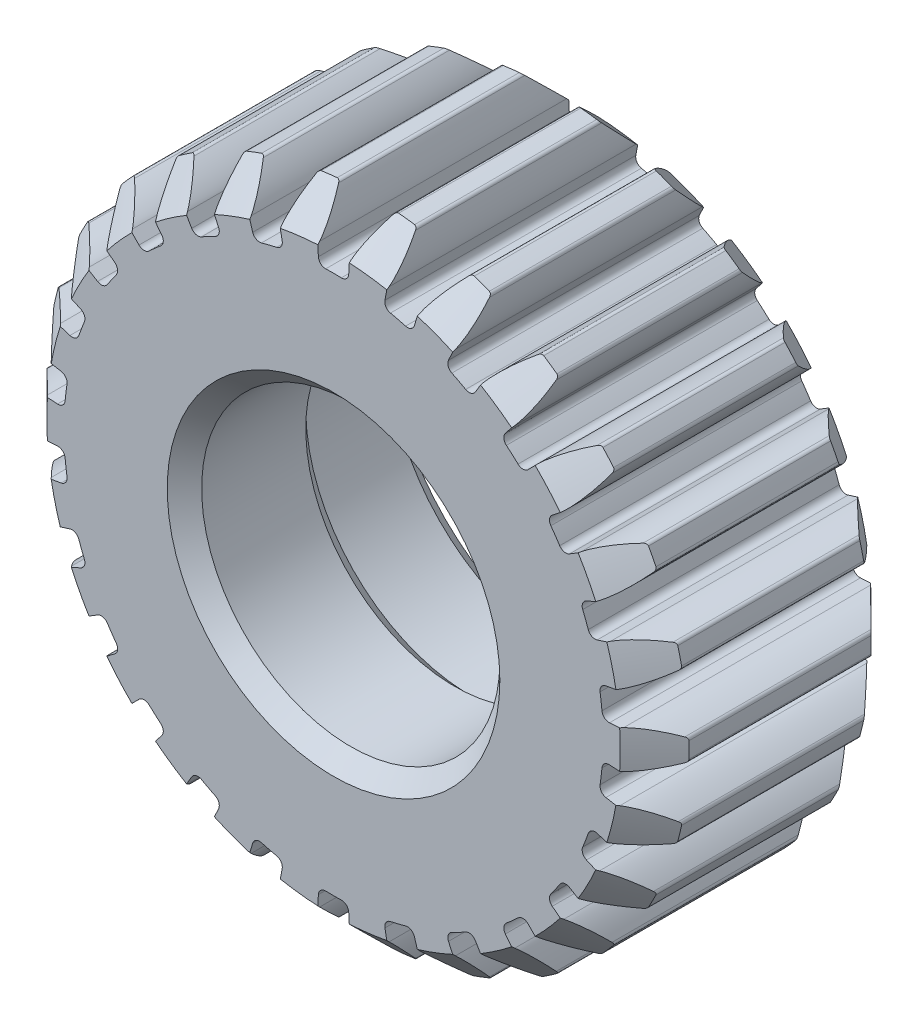
SolidWorks part; units mm, degrees
material "ABS"
ref_plane "Front" through (0, 0, 0) normal (0, 0, 1) x (1, 0, 0)
ref_plane "Top" through (0, 0, 0) normal (0, 1, 0) x (1, 0, 0)
ref_plane "Right" through (0, 0, 0) normal (1, 0, 0) x (0, 0, -1)
sketch "Sketch1" plane through (0, 0, 0) normal (0, 0, 1) x (1, 0, 0)
  circle A0 centre (0, 0) radius 14.224
  dimension "OutsideDiameter" = 28.448
extrude "Boss-Extrude1" add sketch "Sketch1" along normal blind 11.1125
sketch "Sketch3" plane through (0, 0, 0) normal (0, 0, 1) x (1, 0, 0)
  line L0 (0, 0) -> (43.7181, 0) construction
  line L2 (0, 0) -> (-0.6547, 11.92) construction
  line L3 (0, 0) -> (0.6547, 11.92) construction
  line L4 (0.6547, 11.92) -> (0.7013, 12.768) construction
  line L5 (0, 0) -> (0, 61.276) construction
  line L6 (-0.6547, 11.92) -> (-0.7013, 12.768) construction
  circle A0 centre (0, 0) radius 14.224 construction
  circle A1 centre (0, 0) radius 13.208 construction
  circle A2 centre (0, 0) radius 12.7873 construction
  arc A3 (0.6547, 11.92) -> (-0.6547, 11.92) centre (0, 0) ccw construction
  arc A5 (1.2601, 14.1681) -> (-1.2601, 14.1681) centre (0, 0) ccw
  spline S0 degree 4 poles (-0.7013, 12.768) (-0.7014, 12.7703) (-0.7019, 12.7766) (-0.7031, 12.7884) (-0.7055, 12.8077) (-0.709, 12.8323) (-0.7143, 12.864) (-0.7215, 12.9013) (-0.7302, 12.9422) (-0.7407, 12.9866) (-0.752, 13.0308) (-0.7641, 13.0749) (-0.777, 13.1187) (-0.7933, 13.1717) (-0.8142, 13.2351) (-0.8403, 13.3091) (-0.872, 13.3928) (-0.9064, 13.4778) (-0.9422, 13.5612) (-0.9804, 13.6452) (-1.0189, 13.7264) (-1.061, 13.8104) (-1.1009, 13.8878) (-1.148, 13.9742) (-1.1867, 14.0438) (-1.2403, 14.1353) (-1.2727, 14.1892) (-1.3115, 14.2522) (-1.3292, 14.2801) (-1.3401, 14.2973) knots 0 0 0 0 0 0.005377 0.015084 0.028532 0.04661 0.064855 0.092111 0.119476 0.146842 0.174209 0.201575 0.228941 0.256307 0.307035 0.361767 0.4165 0.471232 0.525964 0.580697 0.635429 0.690161 0.744894 0.799626 0.854358 0.909091 0.954545 1 1 1 1 1 construction
  spline S1 degree 4 poles (-0.7013, 12.768) (-0.7014, 12.7703) (-0.7019, 12.7766) (-0.7031, 12.7884) (-0.7055, 12.8077) (-0.709, 12.8323) (-0.7143, 12.864) (-0.7215, 12.9013) (-0.7302, 12.9422) (-0.7407, 12.9866) (-0.752, 13.0308) (-0.7641, 13.0749) (-0.777, 13.1187) (-0.7933, 13.1717) (-0.8142, 13.2351) (-0.8403, 13.3091) (-0.872, 13.3928) (-0.9064, 13.4778) (-0.9422, 13.5612) (-0.9804, 13.6452) (-1.0189, 13.7264) (-1.061, 13.8104) (-1.1009, 13.8878) (-1.148, 13.9742) (-1.1867, 14.0438) (-1.2287, 14.1154) (-1.2494, 14.1503) (-1.2601, 14.1681) knots 0 0 0 0 0 0.005377 0.015084 0.028532 0.04661 0.064855 0.092111 0.119476 0.146842 0.174209 0.201575 0.228941 0.256307 0.307035 0.361767 0.4165 0.471232 0.525964 0.580697 0.635429 0.690161 0.744894 0.799626 0.854358 0.909091 0.909091 0.909091 0.909091 0.909091
  spline S2 degree 4 poles (0.7013, 12.768) (0.7014, 12.7703) (0.7019, 12.7766) (0.7031, 12.7884) (0.7055, 12.8077) (0.709, 12.8323) (0.7143, 12.864) (0.7215, 12.9013) (0.7302, 12.9422) (0.7407, 12.9866) (0.752, 13.0308) (0.7641, 13.0749) (0.777, 13.1187) (0.7933, 13.1717) (0.8142, 13.2351) (0.8403, 13.3091) (0.872, 13.3928) (0.9064, 13.4778) (0.9422, 13.5612) (0.9804, 13.6452) (1.0189, 13.7264) (1.061, 13.8104) (1.1009, 13.8878) (1.148, 13.9742) (1.1867, 14.0438) (1.2403, 14.1353) (1.2727, 14.1892) (1.3115, 14.2522) (1.3292, 14.2801) (1.3401, 14.2973) knots 0 0 0 0 0 0.005377 0.015084 0.028532 0.04661 0.064855 0.092111 0.119476 0.146842 0.174209 0.201575 0.228941 0.256307 0.307035 0.361767 0.4165 0.471232 0.525964 0.580697 0.635429 0.690161 0.744894 0.799626 0.854358 0.909091 0.954545 1 1 1 1 1 construction
  spline S3 degree 4 poles (0.7013, 12.768) (0.7014, 12.7703) (0.7019, 12.7766) (0.7031, 12.7884) (0.7055, 12.8077) (0.709, 12.8323) (0.7143, 12.864) (0.7215, 12.9013) (0.7302, 12.9422) (0.7407, 12.9866) (0.752, 13.0308) (0.7641, 13.0749) (0.777, 13.1187) (0.7933, 13.1717) (0.8142, 13.2351) (0.8403, 13.3091) (0.872, 13.3928) (0.9064, 13.4778) (0.9422, 13.5612) (0.9804, 13.6452) (1.0189, 13.7264) (1.061, 13.8104) (1.1009, 13.8878) (1.148, 13.9742) (1.1867, 14.0438) (1.2287, 14.1154) (1.2494, 14.1503) (1.2601, 14.1681) knots 0 0 0 0 0 0.005377 0.015084 0.028532 0.04661 0.064855 0.092111 0.119476 0.146842 0.174209 0.201575 0.228941 0.256307 0.307035 0.361767 0.4165 0.471232 0.525964 0.580697 0.635429 0.690161 0.744894 0.799626 0.854358 0.909091 0.909091 0.909091 0.909091 0.909091
  point P0 (0, 11.938)
  dimension "OutsideDiameter" = 28.448
  dimension "PitchCircle" = 26.416
  dimension "BaseCircle" = 25.5746
  dimension "DedendumCircle" = 23.876
sketch "DCLTBC" plane through (0, 0, 0) normal (0, 0, 1) x (1, 0, 0)
  line L0 (0, 0) -> (41.04, 0) construction
  line L1 (-0.6547, 11.92) -> (-0.7013, 12.768) construction
  line L2 (0.6547, 11.92) -> (0.7013, 12.768) construction
  line L3 (-0.6547, 11.92) -> (-0.7013, 12.768)
  line L4 (0.6547, 11.92) -> (0.7013, 12.768)
  line L5 (0, 0) -> (0, 104.9356) construction
  circle A0 centre (0, 0) radius 14.224
  circle A1 centre (0, 0) radius 13.208 construction
  circle A2 centre (0, 0) radius 12.7873 construction
  arc A3 (0.6547, 11.92) -> (-0.6547, 11.92) centre (0, 0) ccw construction
  arc A4 (0.6547, 11.92) -> (-0.6547, 11.92) centre (0, 0) ccw
  spline S0 degree 4 poles (-1994.3618, -145.1347) (-17.1064, 10.8202) (-0.8523, 12.0352) (-0.6598, 12.4317) (-0.7055, 12.8077) (-0.709, 12.8323) (-0.7143, 12.864) (-0.7215, 12.9013) (-0.7302, 12.9422) (-0.7407, 12.9866) (-0.752, 13.0308) (-0.7641, 13.0749) (-0.777, 13.1187) (-0.7933, 13.1717) (-0.8142, 13.2351) (-0.8403, 13.3091) (-0.872, 13.3928) (-0.9064, 13.4778) (-0.9422, 13.5612) (-0.9804, 13.6452) (-1.0189, 13.7264) (-1.061, 13.8104) (-1.1009, 13.8878) (-1.148, 13.9742) (-1.4023, 14.4316) (-2.5651, 16.2513) (18.7364, -19.3109) (-1033.241, 1727.2731) knots -0.861068 -0.861068 -0.861068 -0.861068 -0.861068 0.005377 0.015084 0.028532 0.04661 0.064855 0.092111 0.119476 0.146842 0.174209 0.201575 0.228941 0.256307 0.307035 0.361767 0.4165 0.471232 0.525964 0.580697 0.635429 0.690161 0.744894 0.799626 0.854358 2.128331 2.128331 2.128331 2.128331 2.128331 only from (-0.7013, 12.768) to (-1.2601, 14.1681) construction
  spline S1 degree 4 poles (1994.3618, -145.1346) (17.1064, 10.8202) (0.8523, 12.0352) (0.6598, 12.4317) (0.7055, 12.8077) (0.709, 12.8323) (0.7143, 12.864) (0.7215, 12.9013) (0.7302, 12.9422) (0.7407, 12.9866) (0.752, 13.0308) (0.7641, 13.0749) (0.777, 13.1187) (0.7933, 13.1717) (0.8142, 13.2351) (0.8403, 13.3091) (0.872, 13.3928) (0.9064, 13.4778) (0.9422, 13.5612) (0.9804, 13.6452) (1.0189, 13.7264) (1.061, 13.8104) (1.1009, 13.8878) (1.148, 13.9742) (1.4023, 14.4316) (2.5651, 16.2513) (-18.7364, -19.3109) (1033.241, 1727.2731) knots -0.861068 -0.861068 -0.861068 -0.861068 -0.861068 0.005377 0.015084 0.028532 0.04661 0.064855 0.092111 0.119476 0.146842 0.174209 0.201575 0.228941 0.256307 0.307035 0.361767 0.4165 0.471232 0.525964 0.580697 0.635429 0.690161 0.744894 0.799626 0.854358 2.128331 2.128331 2.128331 2.128331 2.128331 only from (0.7013, 12.768) to (1.2601, 14.1681) construction
  spline S2 degree 4 poles (-0.7013, 12.768) (-0.7014, 12.7703) (-0.7019, 12.7766) (-0.7031, 12.7884) (-0.7055, 12.8077) (-0.709, 12.8323) (-0.7143, 12.864) (-0.7215, 12.9013) (-0.7302, 12.9422) (-0.7407, 12.9866) (-0.752, 13.0308) (-0.7641, 13.0749) (-0.777, 13.1187) (-0.7933, 13.1717) (-0.8142, 13.2351) (-0.8403, 13.3091) (-0.872, 13.3928) (-0.9064, 13.4778) (-0.9422, 13.5612) (-0.9804, 13.6452) (-1.0189, 13.7264) (-1.061, 13.8104) (-1.1009, 13.8878) (-1.148, 13.9742) (-1.1867, 14.0438) (-1.2287, 14.1154) (-1.2494, 14.1503) (-1.2601, 14.1681) knots 0 0 0 0 0 0.005377 0.015084 0.028532 0.04661 0.064855 0.092111 0.119476 0.146842 0.174209 0.201575 0.228941 0.256307 0.307035 0.361767 0.4165 0.471232 0.525964 0.580697 0.635429 0.690161 0.744894 0.799626 0.854358 0.909091 0.909091 0.909091 0.909091 0.909091
  spline S3 degree 4 poles (0.7013, 12.768) (0.7014, 12.7703) (0.7019, 12.7766) (0.7031, 12.7884) (0.7055, 12.8077) (0.709, 12.8323) (0.7143, 12.864) (0.7215, 12.9013) (0.7302, 12.9422) (0.7407, 12.9866) (0.752, 13.0308) (0.7641, 13.0749) (0.777, 13.1187) (0.7933, 13.1717) (0.8142, 13.2351) (0.8403, 13.3091) (0.872, 13.3928) (0.9064, 13.4778) (0.9422, 13.5612) (0.9804, 13.6452) (1.0189, 13.7264) (1.061, 13.8104) (1.1009, 13.8878) (1.148, 13.9742) (1.1867, 14.0438) (1.2287, 14.1154) (1.2494, 14.1503) (1.2601, 14.1681) knots 0 0 0 0 0 0.005377 0.015084 0.028532 0.04661 0.064855 0.092111 0.119476 0.146842 0.174209 0.201575 0.228941 0.256307 0.307035 0.361767 0.4165 0.471232 0.525964 0.580697 0.635429 0.690161 0.744894 0.799626 0.854358 0.909091 0.909091 0.909091 0.909091 0.909091
  dimension "OutsideDiameter" = 28.448
  dimension "PitchCircle" = 26.416
  dimension "BaseCircle" = 25.5746
extrude "Cut-Extrude-DCLTBC" cut sketch "DCLTBC" along normal through all
fillet "Fillet-Tip-DCLTBC" radius 0.1588 2 edges at (1.2601, 14.1681, 5.5562) (-1.2601, 14.1681, 5.5562)
fillet "Fillet-Root-DCLTBC" radius 0.3176 2 edges at (-0.6547, 11.92, 5.5562) (0.6547, 11.92, 5.5562)
pattern_circular "CirPattern-DCLTBC" count 26 over 360 about axis through (0, 0, 11.1125) along (0, 0, 1) of "Cut-Extrude-DCLTBC", "Fillet-Tip-DCLTBC", "Fillet-Root-DCLTBC"
sketch "DCGTBC" [suppressed] plane through (0, 0, 0) normal (0, 0, 1) x (1, 0, 0)
  line L0 (0, 0) -> (41.04, 0) construction
  line L1 (-37.3224, 3.2653) -> (0, 0) construction
  line L2 (0, 0) -> (37.3224, 3.2653) construction
  line L3 (0, 0) -> (-16.5124, 0)
  line L5 (0, 0) -> (0, 104.9356) construction
  circle A0 centre (0, 0) radius 38.608
  circle A1 centre (0, 0) radius 38.1 construction
  circle A2 centre (0, 0) radius 36.8864 construction
  arc A3 (0.1846, 37.4645) -> (-0.1846, 37.4645) centre (0, 0) ccw construction
  arc A11 (37.3224, 3.2653) -> (-37.3224, 3.2653) centre (0, 0) ccw
  spline S4 degree 4 poles (999.1092, -9.1639) (9.2917, 35.7604) (0.2917, 36.1338) (0.1647, 36.5321) (0.1834, 36.9323) (0.1852, 36.961) (0.188, 36.9982) (0.192, 37.0421) (0.197, 37.0904) (0.2032, 37.143) (0.21, 37.1956) (0.2175, 37.2482) (0.2254, 37.3006) (0.2357, 37.3641) (0.2489, 37.4405) (0.2657, 37.53) (0.2863, 37.6318) (0.309, 37.7359) (0.3327, 37.8385) (0.3583, 37.9426) (0.3842, 38.0436) (0.4127, 38.1489) (0.4399, 38.2463) (0.4722, 38.3558) (0.6183, 38.8417) (1.2009, 40.5477) (-6.8048, 15.7351) (309.5446, 989.6637) knots -0.780323 -0.780323 -0.780323 -0.780323 -0.780323 0.005377 0.015084 0.028532 0.04661 0.064855 0.092111 0.119476 0.146842 0.174209 0.201575 0.228941 0.256307 0.307035 0.361767 0.4165 0.471232 0.525964 0.580697 0.635429 0.690161 0.744894 0.799626 0.854358 1.89102 1.89102 1.89102 1.89102 1.89102 only from (0.1817, 36.886) to (0.5498, 38.6041) construction
  spline S5 degree 4 poles (-999.1092, -9.1639) (-9.2917, 35.7604) (-0.2917, 36.1338) (-0.1647, 36.5321) (-0.1834, 36.9323) (-0.1852, 36.961) (-0.188, 36.9982) (-0.192, 37.0421) (-0.197, 37.0904) (-0.2032, 37.143) (-0.21, 37.1956) (-0.2175, 37.2482) (-0.2254, 37.3006) (-0.2357, 37.3641) (-0.2489, 37.4405) (-0.2657, 37.53) (-0.2863, 37.6318) (-0.309, 37.7359) (-0.3327, 37.8385) (-0.3583, 37.9426) (-0.3842, 38.0436) (-0.4127, 38.1489) (-0.4399, 38.2463) (-0.4722, 38.3558) (-0.6183, 38.8417) (-1.2009, 40.5477) (6.8048, 15.7351) (-309.5446, 989.6637) knots -0.780323 -0.780323 -0.780323 -0.780323 -0.780323 0.005377 0.015084 0.028532 0.04661 0.064855 0.092111 0.119476 0.146842 0.174209 0.201575 0.228941 0.256307 0.307035 0.361767 0.4165 0.471232 0.525964 0.580697 0.635429 0.690161 0.744894 0.799626 0.854358 1.89102 1.89102 1.89102 1.89102 1.89102 only from (-0.1817, 36.886) to (-0.5498, 38.6041) construction
  spline S6 degree 4 poles (0.1817, 36.886) (0.1818, 36.8886) (0.1819, 36.8959) (0.1824, 36.9097) (0.1834, 36.9323) (0.1852, 36.961) (0.188, 36.9982) (0.192, 37.0421) (0.197, 37.0904) (0.2032, 37.143) (0.21, 37.1956) (0.2175, 37.2482) (0.2254, 37.3006) (0.2357, 37.3641) (0.2489, 37.4405) (0.2657, 37.53) (0.2863, 37.6318) (0.309, 37.7359) (0.3327, 37.8385) (0.3583, 37.9426) (0.3842, 38.0436) (0.4127, 38.1489) (0.4399, 38.2463) (0.4722, 38.3558) (0.4989, 38.4444) (0.5279, 38.5364) (0.5423, 38.5812) (0.5498, 38.6041) knots 0 0 0 0 0 0.005377 0.015084 0.028532 0.04661 0.064855 0.092111 0.119476 0.146842 0.174209 0.201575 0.228941 0.256307 0.307035 0.361767 0.4165 0.471232 0.525964 0.580697 0.635429 0.690161 0.744894 0.799626 0.854358 0.909091 0.909091 0.909091 0.909091 0.909091
  spline S7 degree 4 poles (-0.1817, 36.886) (-0.1818, 36.8886) (-0.1819, 36.8959) (-0.1824, 36.9097) (-0.1834, 36.9323) (-0.1852, 36.961) (-0.188, 36.9982) (-0.192, 37.0421) (-0.197, 37.0904) (-0.2032, 37.143) (-0.21, 37.1956) (-0.2175, 37.2482) (-0.2254, 37.3006) (-0.2357, 37.3641) (-0.2489, 37.4405) (-0.2657, 37.53) (-0.2863, 37.6318) (-0.309, 37.7359) (-0.3327, 37.8385) (-0.3583, 37.9426) (-0.3842, 38.0436) (-0.4127, 38.1489) (-0.4399, 38.2463) (-0.4722, 38.3558) (-0.4989, 38.4444) (-0.5279, 38.5364) (-0.5423, 38.5812) (-0.5498, 38.6041) knots 0 0 0 0 0 0.005377 0.015084 0.028532 0.04661 0.064855 0.092111 0.119476 0.146842 0.174209 0.201575 0.228941 0.256307 0.307035 0.361767 0.4165 0.471232 0.525964 0.580697 0.635429 0.690161 0.744894 0.799626 0.854358 0.909091 0.909091 0.909091 0.909091 0.909091
  dimension "D1" = 5
  dimension "D2" = 5
  dimension "OutsideDiameter" = 28.448
  dimension "PitchCircle" = 26.416
  dimension "BaseCircle" = 25.5746
extrude "Cut-Extrude-DCGTBC" [suppressed] cut sketch "DCGTBC" along normal through all
fillet "Fillet-Tip-DCGTBC" [suppressed] radius 0.1588
pattern_circular "CirPattern-DCGTBC" [suppressed] count 26 over 360
sketch "Sketch4" plane through (0, 0, 11.1125) normal (0, 0, 1) x (1, 0, 0)
  line L0 (-2.4692, -2.0955) -> (2.4692, -2.0955)
  arc A0 (2.4692, -2.0955) -> (-2.4692, -2.0955) centre (0, 0) ccw
  circle A1 centre (0, 0) radius 7.9375
  point P3 (0, 3.2385)
  dimension "D1" = 6.477
  dimension "D3" = 15.875
  dimension "D2" = 5.334
extrude "Cut-Extrude2" cut sketch "Sketch4" against normal through all contours L0 A0 | A1 A0 L0
sketch "Sketch5" plane through (0, 0, 11.1125) normal (0, 0, 1) x (1, 0, 0)
  line L0 (-2.4692, -2.0955) -> (2.4692, -2.0955) construction
  line L1 (-2.4692, -2.0955) -> (2.4692, -2.0955)
  circle A0 centre (0, 0) radius 10.4775
  circle A1 centre (0, 0) radius 7.9375 construction
  arc A2 (2.4692, -2.0955) -> (-2.4692, -2.0955) centre (0, 0) ccw construction
  arc A3 (2.4692, -2.0955) -> (-2.4692, -2.0955) centre (0, 0) ccw
  dimension "D1" = 2.54
extrude "Boss-Extrude2" [suppressed] add sketch "Sketch5" along normal blind 10.16
fillet "Fillet1" [suppressed] radius 2.54
ref_plane "Plane1" [suppressed] through (0, -7.6994, 16.51) normal (0, -1, 0) x (-1, 0, 0)
hole_wizard "#4-40 Tapped Hole1" [suppressed] positions "Sketch8" profile "Sketch7" tap size "#4-40" standard "ANSI Inch"
sketch "Sketch8" [suppressed] plane through (0, -7.6994, 16.51) normal (0, -1, 0) x (-1, 0, 0)
  line L0 (0, 0) -> (0, 7.62) construction
  line L2 (-7.6994, 7.62) -> (7.6994, 7.62) construction
  line L3 (-7.6994, 0) -> (7.6994, 0) construction
  point P12 (0, 3.81)
sketch "Sketch7" plane through (0, -7.6994, 12.7) normal (1, 0, 0) x (0, 0, -1)
  line L0 (0, 0) -> (0, 5.6039)
  line L1 (0, 5.6039) -> (1.1303, 5.6039)
  line L2 (1.1303, 5.6039) -> (1.1303, 0.5328)
  line L3 (1.1303, 0.5328) -> (1.7653, 0)
  line L5 (1.7653, 0) -> (0, 0)
  line L6 (-1.1303, 0.5328) -> (-1.7653, 0) construction
  line L11 (0, -6.35) -> (0, 107.95) construction
  dimension "Thru Tap Drill Dia." = 2.2606
  dimension "Thru Tap Drill Depth" = 5.6039
  dimension "Near C'Sink Dia." = 3.5306
  dimension "Near C'Sink Angle" = 100
cosmetic thread "Hole Thread1" [suppressed] parameters "D2"=2.8448
ref_plane "Plane2" through (0, 0, 5.5562) normal (0, 0, -1) x (-1, 0, 0)
sketch "Sketch10" plane through (0, 0, 0) normal (0, 1, 0) x (1, 0, 0)
  line L0 (14.224, 0) -> (14.224, -1.524)
  line L1 (14.224, -11.1125) -> (14.224, 0) construction
  line L2 (14.224, -1.524) -> (12.7, 0)
  line L3 (14.1235, 0) -> (12.7595, 0) construction
  line L4 (12.7, 0) -> (14.224, 0)
  line L5 (15.5754, -5.5562) -> (-15.5754, -5.5562) construction
  line L6 (12.7, -11.1125) -> (14.224, -11.1125)
  line L7 (14.224, -9.5885) -> (12.7, -11.1125)
  line L8 (14.224, -11.1125) -> (14.224, -9.5885)
  dimension "D1" = 1.524
ref_axis "Axis1" through (0, 0, 0) along (0, 0, 1)
revolve "Cut-Revolve1" cut sketch "Sketch10" angle 360 about axis through (0, 0, 0) along (0, 0, 1)
sketch "Sketch11" plane through (0, 0, 11.1125) normal (0, 0, 1) x (1, 0, 0)
  circle A0 centre (0, 0) radius 7.9375 construction
  circle A1 centre (0, 0) radius 7.9375
  circle A3 centre (0, 0) radius 6.604
  dimension "D1" = 13.208
extrude "Boss-Extrude3" add sketch "Sketch11" against normal up to surface (6.1341 mm away)
chamfer "Chamfer1" distance 0.762 angle 45 3 edges at (6.604, 0, 11.1125) (7.9375, 0, 0) (0, 6.604, 4.9784)
equation "\"DiametralPitch\"= 25'Diametral Pitch"
equation "\"NumTeeth\"= 26'Number of Teeth"
equation "\"PressureAngle\"= 14.5deg'Pressure Angle"
equation "\"Addendum\"= 1 / \"DiametralPitch\"'Addendum"
equation "\"Dedendum\"= 1.25 / \"DiametralPitch\"'Dedendum"
equation "\"WorkingDepth\"= 2 / \"DiametralPitch\"'Working Depth - here for REF (Not used in building model)"
equation "\"WholeDepth\"= 2.25 / \"DiametralPitch\"'Whole Depth - here for REF (Not used in building model)"
equation "\"Clearance\"= .25 / \"DiametralPitch\"'Clearance"
equation "\"CircularPitch\"= pi / \"DiametralPitch\"'Circular Pitch - here for REF (Not used in building model)"
equation "\"PitchCircle\"= \"NumTeeth\" / \"DiametralPitch\"'Pitch Circle - or - Pitch Diameter"
equation "\"OutsideDiameter\"= ( \"NumTeeth\" + 2 ) / \"DiametralPitch\"'Outside Diameter"
equation "\"Fillet_Root\"= \"Clearance\" * cos ( \"PressureAngle\" ) * tan ( ( 90 + \"PressureAngle\" ) / 2 ) 'Fillet Root"
equation "\"AddendumCircle\"= \"PitchCircle\" + ( 2 * \"Addendum\" )'Addendum Circle - or - Addendum Diameter"
equation "\"DedendumCircle\"= \"PitchCircle\" - ( 2 * \"Dedendum\" )'Dedendum Circle - or - Dedendum Diameter"
equation "\"BaseCircle\"= \"PitchCircle\" * cos ( \"PressureAngle\" )'Base Circle - Base Diameter"
equation "\"PitchAngle\"= 360deg / \"NumTeeth\"'Pitch Angle"
equation "\"Alpha\"= sqr ( \"PitchCircle\" ^ 2 - \"BaseCircle\" ^ 2 ) / \"BaseCircle\" * 180 / PI - \"PressureAngle\"'Alpha - Used for Calculating Beta"
equation "\"Beta\"= ( \"PitchAngle\" / 4 - ( \"Alpha\" - 90 ) )'Beta - Used in definition of the parameters for the parametric equation driven curve"
equation "\"Gamma\"= ( \"PitchAngle\" / 4 - ( \"Alpha\" + 90 ) )'Gamma - Used in definition of the parameters for the parametric equation driven curve"
equation "\"Phi\"= sqr ( ( \"AddendumCircle\" / 2 ) ^ 2 - ( \"BaseCircle\" / 2 ) ^ 2 ) / ( \"BaseCircle\" / 2 )'Phi - Used in definition of the parameters for the parametric equation driven curve"
equation "\"DCGTBC\"= iif ( \"DedendumCircle\" > \"BaseCircle\" , \"unsuppressed\" , \"suppressed\" )'if Dedendum Circle IS GREATER THAN BaseCircle THEN UnsuppressORSuppress FEATURE"
equation "\"DCLTBC\"= iif ( \"DedendumCircle\" - .002 > \"BaseCircle\" , \"suppressed\" , \"unsuppressed\" )'if Dedendum Circle - .002 IS GREATER THAN BaseCircle THEN SuppressORUnsuppress FEATURE"
equation "\"Cut-Extrude-DCGTBC\"= iif ( \"DedendumCircle\" > \"BaseCircle\" , \"unsuppressed\" , \"suppressed\" )'if Dedendum Circle IS GREATER THAN BaseCircle THEN UnsuppressORSuppress FEATURE"
equation "\"Cut-Extrude-DCLTBC\"= iif ( \"DedendumCircle\" - .002 > \"BaseCircle\" , \"suppressed\" , \"unsuppressed\" )'if Dedendum Circle - .002 IS GREATER THAN BaseCircle THEN SuppressORUnsuppress FEATURE"
equation "\"CirPattern-DCGTBC\"= iif ( \"DedendumCircle\" > \"BaseCircle\" , \"unsuppressed\" , \"suppressed\" )'if Dedendum Circle IS GREATER THAN BaseCircle THEN UnsuppressORSuppress FEATURE"
equation "\"CirPattern-DCLTBC\"= iif ( \"DedendumCircle\" - .002 > \"BaseCircle\" , \"suppressed\" , \"unsuppressed\" )'if Dedendum Circle - .002 IS GREATER THAN BaseCircle THEN SuppressORUnsuppress FEATURE"
equation "\"Fillet-Tip-DCGTBC\"= iif ( \"DedendumCircle\" > \"BaseCircle\" , \"unsuppressed\" , \"suppressed\" )'if Dedendum Circle IS GREATER THAN BaseCircle THEN UnsuppressORSuppress FEATURE"
equation "\"Fillet-Tip-DCLTBC\"= iif ( \"DedendumCircle\" - .002 > \"BaseCircle\" , \"suppressed\" , \"unsuppressed\" )'if Dedendum Circle - .002 IS GREATER THAN BaseCircle THEN SuppressORUnsuppress FEATURE"
equation "\"Fillet-Root-DCLTBC\"= iif ( \"DedendumCircle\" - .002 > \"BaseCircle\" , \"suppressed\" , \"unsuppressed\" )'if Dedendum Circle - .002 IS GREATER THAN BaseCircle THEN SuppressORUnsuppress FEATURE"
equation "\"D1@CirPattern-DCGTBC\"= \"NumTeeth\"'Number of Teeth"
equation "\"D1@CirPattern-DCLTBC\"= \"NumTeeth\"'Number of Teeth"
equation "\"D1@Fillet-Tip-DCGTBC\"= \"Fillet_Root\" / 2 'Tip Rad For Large No of Teeth"
equation "\"D1@Fillet-Tip-DCLTBC\"=\"Fillet_Root\" / 2'Tip Rad For Small No of Teeth"
equation "\"D1@Fillet-Root-DCLTBC\"= \"Fillet_Root\"'Fillet Root"
